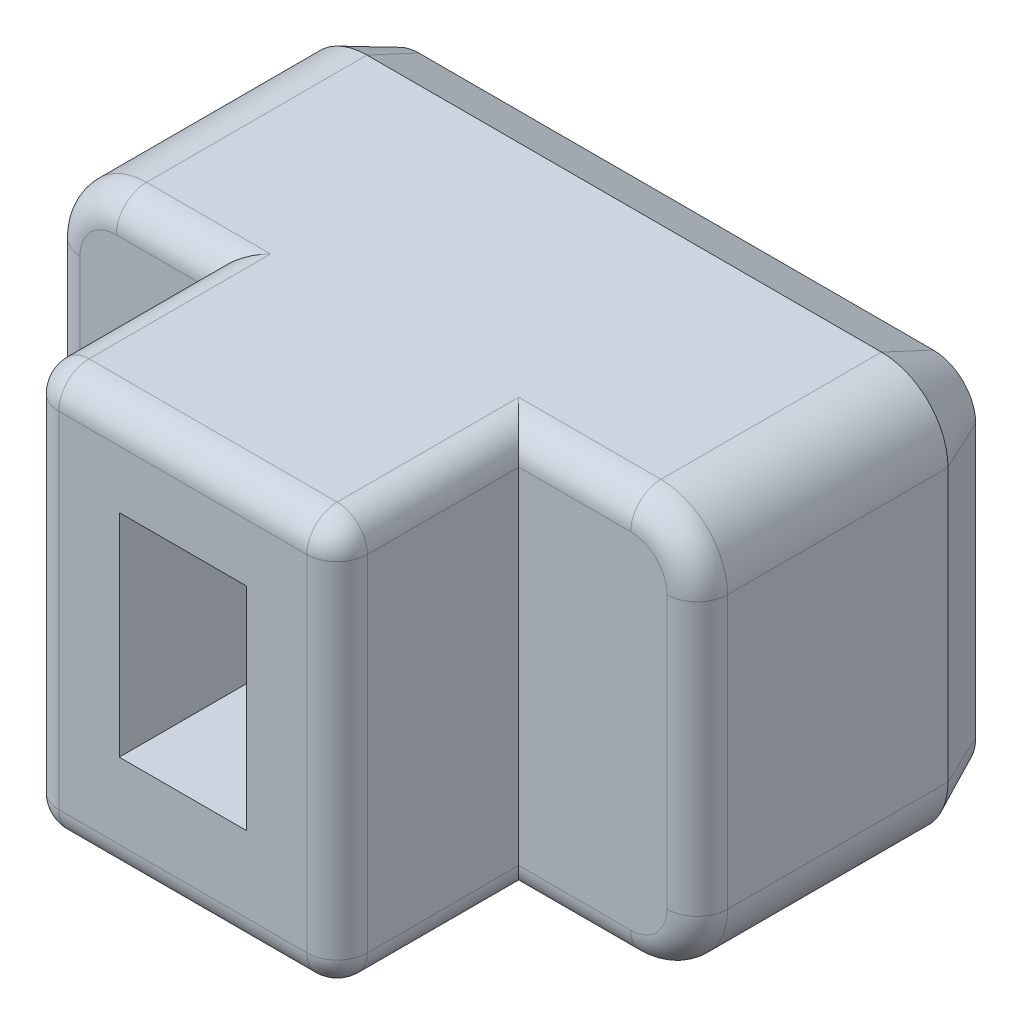
SolidWorks part; units mm, degrees
ref_plane "Plan de face" through (0, 0, 0) normal (0, 0, 1) x (1, 0, 0)
ref_plane "Plan de dessus" through (0, 0, 0) normal (0, 1, 0) x (1, 0, 0)
ref_plane "Plan de droite" through (0, 0, 0) normal (1, 0, 0) x (0, 0, -1)
sketch "Esquisse2" plane through (0, 0, 0) normal (0, 0, 1) x (1, 0, 0)
  line L1 (1.1, 0) -> (9.6, 0)
  line L2 (0, 1.1) -> (0, 5.6)
  line L3 (1.1, 6.7) -> (9.6, 6.7)
  line L4 (10.7, 1.1) -> (10.7, 5.6)
  arc A0 (9.6, 6.7) -> (10.7, 5.6) centre (9.6, 5.6) cw
  arc A1 (9.6, 0) -> (10.7, 1.1) centre (9.6, 1.1) ccw
  arc A2 (1.1, 0) -> (0, 1.1) centre (1.1, 1.1) cw
  arc A3 (0, 5.6) -> (1.1, 6.7) centre (1.1, 5.6) cw
  point P7 (10.7, 6.7)
  point P12 (0, 0)
  point P15 (0, 6.7)
  dimension "D3" = 1.1
  dimension "D1" = 10.7
  dimension "D2" = 6.7
extrude "Boss.-Extru.1" add sketch "Esquisse2" along normal blind 8
sketch "Esquisse3" plane through (0, 0, 8) normal (0, 0, 1) x (1, 0, 0)
  line L0 (0, 5.6) -> (0, 1.1) construction
  line L1 (4.15, 5.25) -> (6.25, 5.25)
  line L2 (4.15, 5.25) -> (4.15, 1.75)
  line L3 (4.15, 1.75) -> (6.25, 1.75)
  line L4 (6.25, 5.25) -> (6.25, 1.75)
  line L5 (10.7, 1.1) -> (10.7, 5.6) construction
  line L6 (9.6, 6.7) -> (1.1, 6.7) construction
  line L7 (1.1, 0) -> (9.6, 0) construction
  dimension "D1" = 2.1
  dimension "D2" = 3.5
  dimension "D3" = 4.15
  dimension "D4" = 4.45
  dimension "D5" = 1.45
  dimension "D6" = 1.75
extrude "Enlèv. mat.-Extru.1" cut sketch "Esquisse3" against normal blind 3
sketch "Esquisse4" plane through (0, 0, 8) normal (0, 0, 1) x (1, 0, 0)
  line L0 (2.65, 6.7) -> (2.65, 0)
  line L1 (9.6, 6.7) -> (1.1, 6.7) construction
  line L2 (1.1, 0) -> (9.6, 0) construction
  line L3 (2.65, 0) -> (7.75, 0)
  line L4 (7.75, 0) -> (7.75, 6.7)
  line L5 (7.75, 6.7) -> (2.65, 6.7)
  line L6 (4.15, 5.25) -> (4.15, 1.75) construction
  line L7 (6.25, 1.75) -> (6.25, 5.25) construction
  dimension "D1" = 1.5
  dimension "D2" = 1.5
extrude "Enlèv. mat.-Extru.2" cut sketch "Esquisse4" against normal blind 3 flip side to cut
fillet "Congé1" radius 0.5 18 edges at (8.675, 0, 5) (10.3778, 0.3222, 5) (10.7, 3.35, 5) (10.3778, 6.3778, 5) (1.875, 6.7, 5) (0.3222, 6.3778, 5) (1.875, 0, 5) (0.3222, 0.3222, 5) (7.75, 6.7, 6.5) (2.65, 6.7, 6.5) (7.75, 0, 6.5) (2.65, 0, 6.5) (2.65, 3.35, 8) (5.2, 6.7, 8) (7.75, 3.35, 8) (5.2, 0, 8) (8.675, 6.7, 5) (0, 3.35, 5)
chamfer "Chanfrein1" distance 0.4 angle 65 8 edges at (5.35, 0, 0) (10.3778, 0.3222, 0) (0.3222, 0.3222, 0) (10.7, 3.35, 0) (0, 3.35, 0) (10.3778, 6.3778, 0) (0.3222, 6.3778, 0) (5.35, 6.7, 0) first distance on face at (5.35, 3.35, 0)
sketch "Esquisse5" plane through (0, 0, 0) normal (0, 0, 1) x (1, 0, 0)
  line L0 (-0.9378, 5.093) -> (11.6517, 5.093) construction
  text T0 "FPL" font "Corbel" height 3.5
extrude "Enlèv. mat.-Extru.3" cut sketch "Esquisse5" along normal blind 0.2
extrude "Boss.-Extru.2" add sketch "Esquisse5<4>" against normal blind 0.2
sketch "Esquisse5<4>" plane through (0, 0, 0) normal (0, 0, 1) x (1, 0, 0) same geometry as "Esquisse5"
